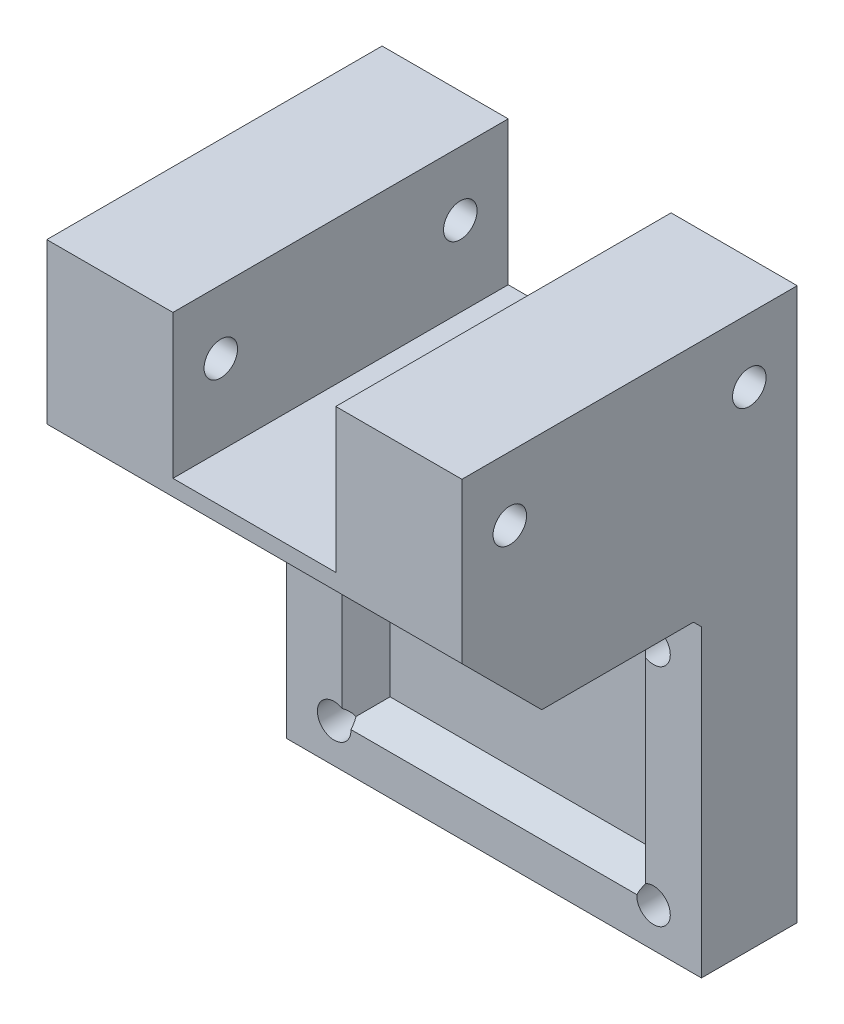
SolidWorks part; units mm, degrees
material "ABS"
ref_plane "Płaszczyzna przednia" through (0, 0, 0) normal (0, 0, 1) x (1, 0, 0)
ref_plane "Płaszczyzna górna" through (0, 0, 0) normal (0, 1, 0) x (1, 0, 0)
ref_plane "Płaszczyzna prawa" through (0, 0, 0) normal (1, 0, 0) x (0, 0, -1)
sketch "Szkic1" plane through (0, 0, 0) normal (0, 0, 1) x (1, 0, 0)
  line L0 (0, 25.3942) -> (0, -31.8647) construction
  line L1 (-26, -19) -> (26, -19)
  line L2 (-26, -19) -> (-26, 19)
  line L3 (-26, 19) -> (26, 19)
  line L4 (26, -19) -> (26, 19)
  line L5 (-26, -19) -> (26, 19) construction
  line L6 (-26, 19) -> (26, -19) construction
  line L7 (-29.318, 0) -> (39.6971, 0) construction
  circle A0 centre (20, 14.1) radius 2.1
  circle A1 centre (20, -14.1) radius 2.1
  circle A2 centre (-20, -14.1) radius 2.1
  circle A3 centre (-20, 14.1) radius 2.1
  point P0 (0, 0)
  dimension "D3" = 4.2
  dimension "D5" = 20
  dimension "D1" = 52
  dimension "D2" = 38
  dimension "D4" = 14.1
extrude "Dodanie-wyciągnięcie1" add sketch "Szkic1" along normal blind 12
sketch "Szkic2" plane through (0, 0, 12) normal (0, 0, 1) x (1, 0, 0)
  line L1 (16, -11) -> (-16, -11)
  line L2 (16, -11) -> (16, 11)
  line L3 (16, 11) -> (-16, 11)
  line L4 (-16, -11) -> (-16, 11)
  line L5 (16, -11) -> (-16, 11) construction
  line L6 (16, 11) -> (-16, -11) construction
  point P0 (0, 0)
  dimension "D1" = 32
  dimension "D2" = 22
extrude "Wytnij-wyciągnięcie1" cut sketch "Szkic2" against normal blind 3
chamfer "Sfazowanie1" distance 3 angle 45 4 edges at (0, -11, 12) (16, 0, 12) (-16, 0, 12) (0, 11, 12)
sketch "Szkic3" plane through (0, 0, 12) normal (0, 0, 1) x (1, 0, 0)
  line L0 (-20, 14.1) -> (-20, 32.1) construction
  line L1 (-10.2, 32.1) -> (10.2, 32.1)
  line L2 (26, 19) -> (-26, 19) construction
  line L3 (-10.2, 32.1) -> (-10.2, 50.1)
  line L4 (-10.2, 50.1) -> (-26, 50.1)
  line L5 (-26, 50.1) -> (-26, 19)
  line L6 (10.2, 32.1) -> (10.2, 50.1)
  line L7 (10.2, 50.1) -> (26, 50.1)
  line L8 (26, 50.1) -> (26, 19)
  line L9 (26, 19) -> (-26, 19)
  point P7 (0, 19)
  dimension "D1" = 18
  dimension "D2" = 20.4
  dimension "D3" = 10.2
  dimension "D4" = 18
extrude "Dodanie-wyciągnięcie2" add sketch "Szkic3" against normal blind 12
sketch "Szkic4" plane through (0, 0, 12) normal (0, 0, 1) x (1, 0, 0)
  line L0 (10.2, 32.1) -> (-10.2, 32.1) construction
  line L5 (0, 42.1305) -> (0, -22.2223) construction
  line L6 (-26, 20.1) -> (26, 20.1)
  line L7 (26, -19) -> (26, 50.1) construction
  line L12 (-26, 50.1) -> (-26, 20.1)
  line L13 (-26, 50.1) -> (-26, -19) construction
  line L14 (26, 20.1) -> (26, 50.1)
  line L15 (26, 50.1) -> (10.2, 50.1) construction
  line L16 (10.2, 50.1) -> (10.2, 32.1) construction
  line L17 (-10.2, 32.1) -> (-10.2, 50.1) construction
  line L18 (-10.2, 50.1) -> (-26, 50.1) construction
  line L19 (26, 50.1) -> (10.2, 50.1)
  line L20 (10.2, 50.1) -> (10.2, 32.1)
  line L21 (10.2, 32.1) -> (-10.2, 32.1)
  line L22 (-10.2, 32.1) -> (-10.2, 50.1)
  line L23 (-10.2, 50.1) -> (-26, 50.1)
  dimension "D1" = 12
extrude "Dodanie-wyciągnięcie3" add sketch "Szkic4" along normal blind 30
chamfer "Sfazowanie2" distance 1 angle 45 1 edges at (0, 20.1, 12)
sketch "Szkic6" plane through (26, 0, 0) normal (1, 0, 0) x (0, 0, -1)
  line L0 (0, 32.1) -> (-42, 32.1) construction
  line L1 (0, 32.1) -> (-42, 32.1) construction
  line L2 (-42, 20.1) -> (-42, 50.1) construction
  line L3 (-21, 32.1) -> (-21, 53.9853) construction
  circle A0 centre (-36, 42.1) radius 2.1
  circle A1 centre (-6, 42.1) radius 2.1
  dimension "D1" = 4.2
  dimension "D2" = 6
  dimension "D3" = 10
extrude "Wytnij-wyciągnięcie2" cut sketch "Szkic6" against normal through all
chamfer "Sfazowanie3" distance 10 angle 45 1 edges at (0, 20.1, 42)
